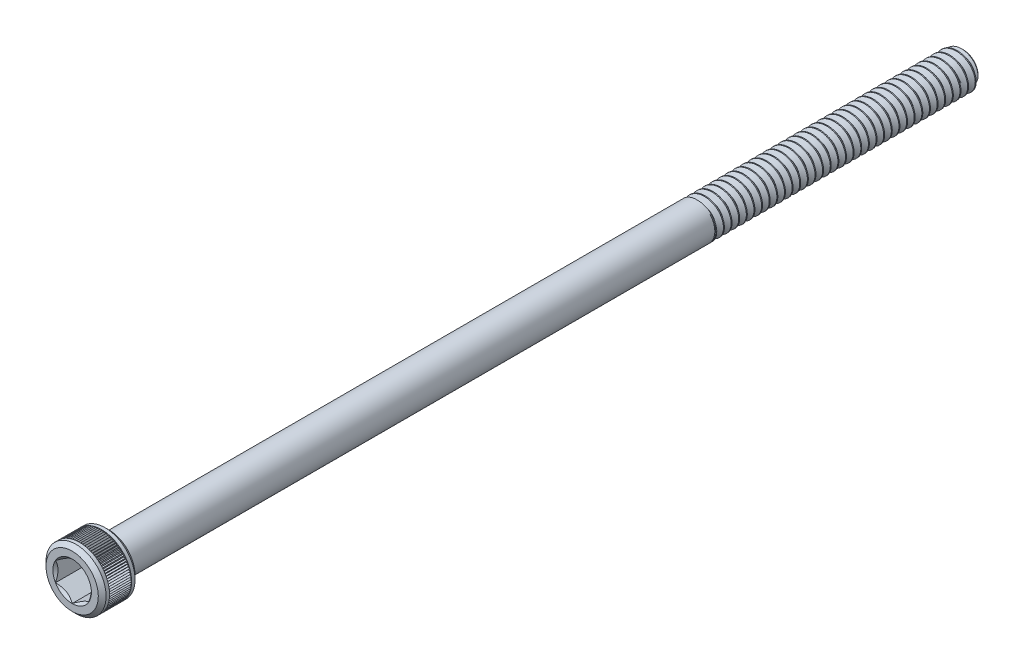
SolidWorks part; units mm, degrees
ref_plane "Front Plane" through (0, 0, 0) normal (0, 0, 1) x (1, 0, 0)
ref_plane "Top Plane" through (0, 0, 0) normal (0, 1, 0) x (1, 0, 0)
ref_plane "Right Plane" through (0, 0, 0) normal (1, 0, 0) x (0, 0, -1)
sketch "Sketch1" plane through (0, 0, 0) normal (1, 0, 0) x (0, 0, -1)
  line L0 (-34.925, 0) -> (15.875, 0) construction
  line L1 (-34.925, 1.7859) -> (-34.925, -1.7859) construction
  line L2 (15.875, 1.0922) -> (15.875, -1.0922) construction
  line L3 (15.875, 1.0922) -> (16.3286, 1.0922) construction
  line L4 (-34.925, 1.7859) -> (-37.1094, 1.7859) construction
  line L5 (-37.1094, -0.9922) -> (-37.1094, 0.9922) construction
  point P5 (0, 1.0922)
  point P6 (14.7411, -1.0922)
  point P9 (15.875, 0)
  point P14 (-37.1094, 0)
  point P15 (-30.5562, 0)
  point P16 (-4.3688, 0)
  point P17 (-36.6725, 1.7859)
  point P18 (-35.3619, 1.7859)
  dimension "Pitch" = 0.4536
  dimension "Thread OD" = 2.1844
  dimension "Minimum Thread Length" = 15.875
  dimension "Head Diameter" = 3.5719
  dimension "Head Height" = 2.1844
  dimension "Length" = 50.8
  dimension "Drive Size" = 1.9844
  dimension "D1" = 1.1339
  dimension "D2" = 4.3688
  dimension "D3" = 4.3688
  dimension "D4" = 0.4369
  dimension "D5" = 0.4369
sketch "Sketch12" plane through (0, 0, 0) normal (0, 0, 1) x (1, 0, 0)
  line L0 (-0.0624, 1.7859) -> (0.0624, 1.7859)
  line L1 (0.0624, 1.7859) -> (0, 1.6779)
  line L2 (0, 1.6779) -> (-0.0624, 1.7859)
  line L3 (-0.0624, 1.7859) -> (0, 0) construction
  line L4 (0, 0) -> (0.0624, 1.7859) construction
  dimension "Knurl Angle" = 4
sketch "Sketch2" plane through (0, 0, 0) normal (1, 0, 0) x (0, 0, -1)
  line L0 (-37.1094, 0) -> (15.875, 0)
  line L1 (-36.8782, 1.7859) -> (-35.1562, 1.7859)
  line L2 (-37.1094, 1.5547) -> (-37.1094, 0)
  line L4 (-34.925, 1.5547) -> (-34.925, 1.0922)
  line L5 (15.875, 0) -> (15.875, 0.861)
  line L6 (15.6438, 1.0922) -> (-34.925, 1.0922)
  line L7 (-34.925, 1.5547) -> (-35.1562, 1.7859)
  line L8 (-37.1094, 1.5547) -> (-36.8782, 1.7859)
  line L9 (15.6438, 1.0922) -> (15.875, 0.861)
  line L10 (-34.925, 1.7859) -> (-37.1094, 1.7859) construction
  line L11 (-34.925, 1.7859) -> (-34.925, -1.7859) construction
  point P0 (-36.0172, 1.7859)
  dimension "D1" = 45
  dimension "D2" = 0.2312
revolve "Revolve1" add sketch "Sketch2" angle 360 about L0
sketch "Sketch3" plane through (0, 0, 37.1094) normal (0, 0, 1) x (1, 0, 0)
  line L0 (-0.9922, 0) -> (0.9922, 0) construction
  line L1 (0, 1.1457) -> (-0.9922, 0.5728)
  line L2 (-0.9922, 0.5728) -> (-0.9922, -0.5728)
  line L3 (-0.9922, -0.5728) -> (0, -1.1457)
  line L4 (0, -1.1457) -> (0.9922, -0.5728)
  line L5 (0.9922, -0.5728) -> (0.9922, 0.5728)
  line L6 (0.9922, 0.5728) -> (0, 1.1457)
  line L7 (0, -0.9922) -> (0, 0.9922) construction
  circle A0 centre (0, 0) radius 0.9922 construction
extrude "Cut-Extrude1" cut sketch "Sketch3" against normal blind 1.6383
sketch "Sketch4" plane through (0, 0, 37.1094) normal (0, 0, 1) x (1, 0, 0)
  circle A0 centre (0, 0) radius 1.1457
extrude "Cut-Extrude2" cut sketch "Sketch4" against normal through all draft 45
split "Split1" trim tools "Front Plane" bodies to split 106 resulting bodies 107 108
sketch "Sketch6" plane through (0, 0, -15.875) normal (0, 0, -1) x (-1, 0, 0)
  line L0 (0, -0.9922) -> (0, 0.9922) construction
  circle A0 centre (0, 0) radius 1.0922
sketch "Sketch7" plane through (0, 0, 0) normal (1, 0, 0) x (0, 0, -1)
  line L0 (15.875, 1.0922) -> (16.2719, 1.0922) construction
  line L1 (16.2719, 1.0922) -> (16.0734, 0.7485) construction
  line L2 (16.0734, 0.7485) -> (15.875, 1.0922) construction
  line L3 (15.875, 1.0922) -> (15.8467, 1.1413) construction
  line L4 (15.8467, 1.1413) -> (16.3002, 1.1413) construction
  line L5 (16.3002, 1.1413) -> (16.2719, 1.0922) construction
  line L6 (16.0451, 0.7976) -> (16.1018, 0.7976) construction
  line L7 (16.0734, 1.0922) -> (16.0734, 1.1413) construction
  line L8 (16.0734, 0.7976) -> (16.0734, 0.7485) construction
  line L9 (15.875, 1.0922) -> (16.3286, 1.0922) construction
  dimension "D1" = 0.0567
curve "Helix/Spiral1" pitch 0.4536 height 16.7821 radius 1.0922 centre (0, 0, -15.875) axis (0, 0, 1) start towards (0, 1, 0)
sketch "Sketch8" plane through (0, 0, 0) normal (1, 0, 0) x (0, 0, -1)
  line L0 (15.8608, 1.1168) -> (16.286, 1.1168)
  line L1 (15.875, 1.0922) -> (15.8467, 1.1413) construction
  line L2 (16.3002, 1.1413) -> (16.2719, 1.0922) construction
  line L3 (16.286, 1.1168) -> (16.1018, 0.7976)
  line L4 (16.1018, 0.7976) -> (16.0451, 0.7976)
  line L5 (16.0451, 0.7976) -> (15.8608, 1.1168)
sweep "Cut-Sweep1" cut profiles "Sketch8" path "Helix/Spiral1" align with end faces yes
combine bodies "Combine1" operation type add bodies to combine 109 107
sketch "Sketch14" plane through (0, 0, 0) normal (0, 0, 1) x (1, 0, 0)
  line L0 (0.0624, 1.7859) -> (0, 1.6779) construction
  line L1 (0, 1.6779) -> (-0.0624, 1.7859) construction
  line L2 (-0.0624, 1.7859) -> (0.0624, 1.7859) construction
  line L3 (0.0624, 1.7859) -> (0, 1.6779)
  line L4 (0, 1.6779) -> (-0.0624, 1.7859)
  line L5 (-0.0624, 1.7859) -> (0.0624, 1.7859)
extrude "Cut-Extrude3" cut sketch "Sketch14" against normal up to vertex (-35.3619 mm away) from vertex up to point (0, 1.7859, 35.3619) starting at point (0, 1.7859, 36.6725)
pattern_circular "CirPattern1" count 90 over 360 about axis through (0, 0, 34.925) along (0, 0, -1) of "Cut-Extrude3"
equation "\"D1@Cut-Extrude1\"=\"Head Height@Sketch1\"*.75"
equation "\"D2@Sketch2\"=( \"Head Diameter@Sketch1\" - \"Thread OD@Sketch1\" )  / 6"
equation "\"D3@Helix/Spiral1\" = \"Minimum Thread Length@Sketch1\" +  ( 2 * \"Pitch@Sketch1\" ) "
equation "\"D1@Sketch7\"=\"Pitch@Sketch1\"/8"
equation "\"D4@Helix/Spiral1\"=\"Pitch@Sketch1\""
equation "\"D1@Sketch1\"=\"Pitch@Sketch1\"*2.5"
equation "\"D2@Sketch1\"=\"Thread OD@Sketch1\"*2"
equation "\"D3@Sketch1\"=\"D2@Sketch1\""
equation "\"D4@Sketch1\"=\"Head Height@Sketch1\"*.2"
equation "\"D1@CirPattern1\"=360/\"Knurl Angle@Sketch12\""
equation "\"D5@Sketch1\"=\"Head Height@Sketch1\"*.2"
